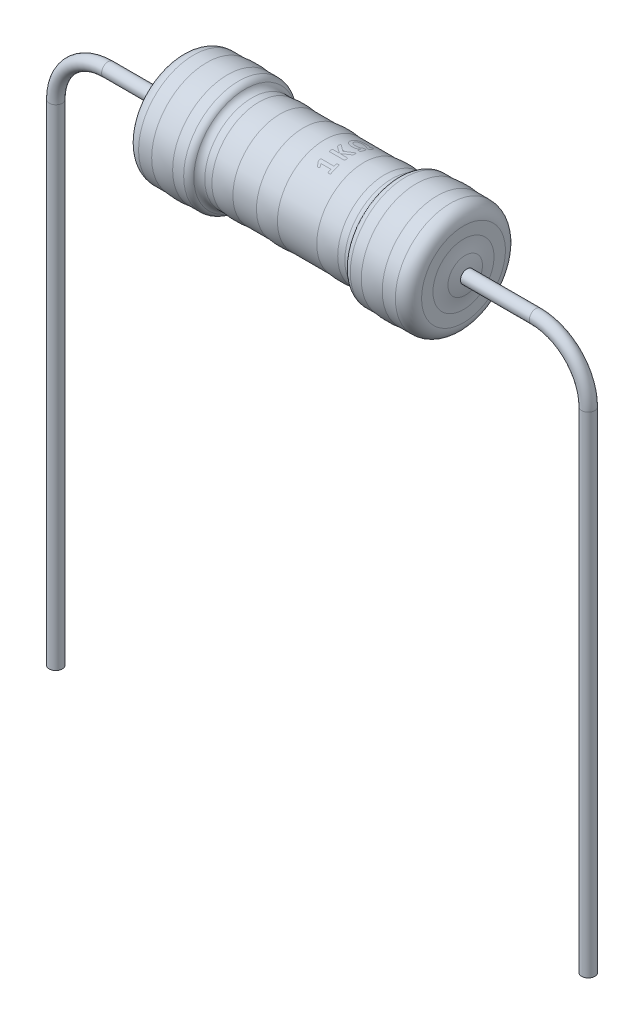
SolidWorks part; units mm, degrees
ref_plane "Front Plane" through (0, 0, 0) normal (0, 0, 1) x (1, 0, 0)
ref_plane "Top Plane" through (0, 0, 0) normal (0, 1, 0) x (1, 0, 0)
ref_plane "Right Plane" through (0, 0, 0) normal (1, 0, 0) x (0, 0, -1)
sketch "Sketch Set Wire Width" plane through (0, 0, 0) normal (0, 0, 1) x (1, 0, 0)
  line L0 (-8.16, 0) -> (8.16, 0)
  line L1 (-10.16, -2) -> (-10.16, -20.6984)
  line L2 (10.16, -2) -> (10.16, -20.6984)
  line L3 (-10.16, -20.6984) -> (10.16, -20.6984) construction
  line L4 (0, 0) -> (0, -20.6984) construction
  arc A0 (-8.16, 0) -> (-10.16, -2) centre (-8.16, -2) ccw
  arc A1 (8.16, 0) -> (10.16, -2) centre (8.16, -2) cw
  dimension "D2" = 2
  dimension "D3" = 60
  dimension "D1" = 20.32
sketch "Sketch Wire Diameter" plane through (0, 0, 0) normal (1, 0, 0) x (0, 0, -1)
  circle A0 centre (0, 0) radius 0.25
  dimension "D1" = 0.5
sweep "SET WIRE LENGTH" add profiles "Sketch Wire Diameter" path "Sketch Set Wire Width"
sketch "Sketch3" plane through (0, 0, 0) normal (0, 0, 1) x (1, 0, 0)
  line L0 (-5.4, 0) -> (5.4, 0)
  line L1 (0, 0) -> (0, 1.8) construction
  line L2 (-2.9, 1.8) -> (2.9, 1.8)
  line L3 (-5.4, 0) -> (-5.4, 1.6)
  line L4 (-4.9, 2.1) -> (-3.18, 2.1)
  line L5 (-2.9, 1.82) -> (-2.9, 1.8)
  line L6 (5.4, 0) -> (5.4, 1.6)
  line L7 (4.9, 2.1) -> (3.18, 2.1)
  line L8 (2.9, 1.82) -> (2.9, 1.8)
  arc A0 (-5.4, 1.6) -> (-4.9, 2.1) centre (-4.9, 1.6) cw
  arc A1 (5.4, 1.6) -> (4.9, 2.1) centre (4.9, 1.6) ccw
  arc A2 (-3.18, 2.1) -> (-2.9, 1.82) centre (-3.18, 1.82) cw
  arc A3 (3.18, 2.1) -> (2.9, 1.82) centre (3.18, 1.82) ccw
  dimension "D5" = 0.5
  dimension "D6" = 0.28
  dimension "D1" = 10.8
  dimension "D2" = 5.8
  dimension "D3" = 1.8
  dimension "D4" = 2.1
revolve "Revolve2" add sketch "Sketch3" angle 360 about L0
fillet "Fillet1" radius 0.3 2 edges at (2.9, 0, 1.8) (-2.9, 0, 1.8)
sketch "Sketch5" plane through (0, 0, 0) normal (0, 0, 1) x (1, 0, 0)
  line L0 (0, 0) -> (2, 0) construction
  line L1 (0, 0) -> (-0.3, 0) construction
  line L2 (-0.3, 0) -> (-2, 0) construction
  line L3 (-2, 0) -> (-4, 0) construction
  line L4 (2, 0) -> (4, 0) construction
  line L5 (-4, 0) -> (-4, 2.1) construction
  line L6 (-0.3, 0) -> (-0.3, 1.8) construction
  line L7 (-2, 0) -> (-2, 1.8) construction
  line L8 (2, 0) -> (2, 1.8) construction
  line L9 (4, 0) -> (4, 2.1) construction
  line L10 (-4, 2.1) -> (-4, 2.13) construction
  line L11 (-4.9, 2.1) -> (-3.18, 2.1) construction
  line L12 (4.9, 2.1) -> (3.18, 2.1) construction
  line L13 (-2.9, 1.8) -> (2.9, 1.8) construction
  line L14 (-2, 1.8) -> (-2, 1.83) construction
  line L17 (-4.4, 2.1) -> (-3.6, 2.1)
  line L19 (-5.4, 0) -> (5.4, 0) construction
  line L22 (-2.4, 1.8) -> (-1.6, 1.8) construction
  line L26 (-0.7, 1.8) -> (0.1, 1.8) construction
  line L30 (1.6, 1.8) -> (2.4, 1.8) construction
  line L34 (3.6, 2.1) -> (4.4, 2.1) construction
  line L36 (-0.3, 1.8) -> (-0.3, 1.83) construction
  line L37 (2, 1.8) -> (2, 1.83) construction
  line L38 (4, 2.1) -> (4, 2.13) construction
  arc A0 (-4.4, 2.1) -> (-3.6, 2.1) centre (-4, -0.5517) cw
  arc A1 (-2.4, 1.8) -> (-1.6, 1.8) centre (-2, -0.8517) cw construction
  arc A2 (-0.7, 1.8) -> (0.1, 1.8) centre (-0.3, -0.8517) cw construction
  arc A3 (1.6, 1.8) -> (2.4, 1.8) centre (2, -0.8517) cw construction
  arc A4 (3.6, 2.1) -> (4.4, 2.1) centre (4, -0.5517) cw construction
  dimension "D3" = 0.8
  dimension "D1" = 4
  dimension "D2" = 4
  dimension "D4" = 0.03
  dimension "D5" = 2
  dimension "D6" = 2
  dimension "D7" = 1.7
revolve "Band 1" add sketch "Sketch5" angle 360 about L2
sketch "Sketch8" plane through (0, 0, 0) normal (0, 0, 1) x (1, 0, 0)
  line L0 (-2.4, 1.8) -> (-1.6, 1.8) construction
  line L1 (-2.4, 1.8) -> (-1.6, 1.8)
  arc A0 (-1.6, 1.8) -> (-2.4, 1.8) centre (-2, -0.8517) ccw construction
  arc A1 (-1.6, 1.8) -> (-2.4, 1.8) centre (-2, -0.8517) ccw
revolve "Band 2" add sketch "Sketch8" angle 360 about L2
sketch "Sketch9" plane through (0, 0, 0) normal (0, 0, 1) x (1, 0, 0)
  line L0 (-0.7, 1.8) -> (0.1, 1.8) construction
  line L1 (-0.7, 1.8) -> (0.1, 1.8)
  arc A0 (0.1, 1.8) -> (-0.7, 1.8) centre (-0.3, -0.8517) ccw construction
  arc A1 (0.1, 1.8) -> (-0.7, 1.8) centre (-0.3, -0.8517) ccw
revolve "Band 3" add sketch "Sketch9" angle 360 about L2
sketch "Sketch10" plane through (0, 0, 0) normal (0, 0, 1) x (1, 0, 0)
  line L0 (1.6, 1.8) -> (2.4, 1.8) construction
  line L1 (1.6, 1.8) -> (2.4, 1.8)
  arc A0 (2.4, 1.8) -> (1.6, 1.8) centre (2, -0.8517) ccw construction
  arc A1 (2.4, 1.8) -> (1.6, 1.8) centre (2, -0.8517) ccw
revolve "Band 4" add sketch "Sketch10" angle 360 about L0
sketch "Sketch11" plane through (0, 0, 0) normal (0, 0, 1) x (1, 0, 0)
  line L0 (3.6, 2.1) -> (4.4, 2.1) construction
  line L1 (3.6, 2.1) -> (4.4, 2.1)
  arc A0 (4.4, 2.1) -> (3.6, 2.1) centre (4, -0.5517) ccw construction
  arc A1 (4.4, 2.1) -> (3.6, 2.1) centre (4, -0.5517) ccw
revolve "Band 5" add sketch "Sketch11" angle 360 about L4
sketch "Sketch12" plane through (0, 0, 0) normal (0, 0, 1) x (1, 0, 0)
  line L0 (-5.35, 0) -> (5.35, 0) construction
  line L1 (-5.35, 1) -> (-5.35, 0)
  line L2 (5.35, 1) -> (5.35, 0)
  line L3 (-5.35, 0) -> (-5.55, 0)
  line L4 (5.35, 0) -> (5.55, 0)
  arc A0 (-5.35, 1) -> (-5.55, 0) centre (-2.95, 0) ccw
  arc A1 (5.35, 1) -> (5.55, 0) centre (2.95, 0) cw
  dimension "D3" = 0.2
  dimension "D4" = 2.6
  dimension "D1" = 10.7
  dimension "D2" = 1
revolve "Revolve10" add sketch "Sketch12" angle 360 about L0
fillet "Fillet2" radius 2 2 edges at (5.4, 0, 0.8703) (-5.4, 0, -0.8703)
ref_plane "Plane2" through (0, 3, 0) normal (0, 1, 0) x (1, 0, 0)
sketch "Sketch13" plane through (0, 3, 0) normal (0, 1, 0) x (1, 0, 0)
  line L0 (0, 0) -> (1.15, 0) construction
  line L1 (1.15, 1.75) -> (1.15, -1.75) construction
  text T0 "1KΩ" font "Calibri" height 0.6
  dimension "D1" = 3.5
  dimension "D2" = 1.15
wrap "Wrap1" sketch "Sketch13" wrap type scribe source sketch "Sketch13" face at (0.1, 1.8, 0)
